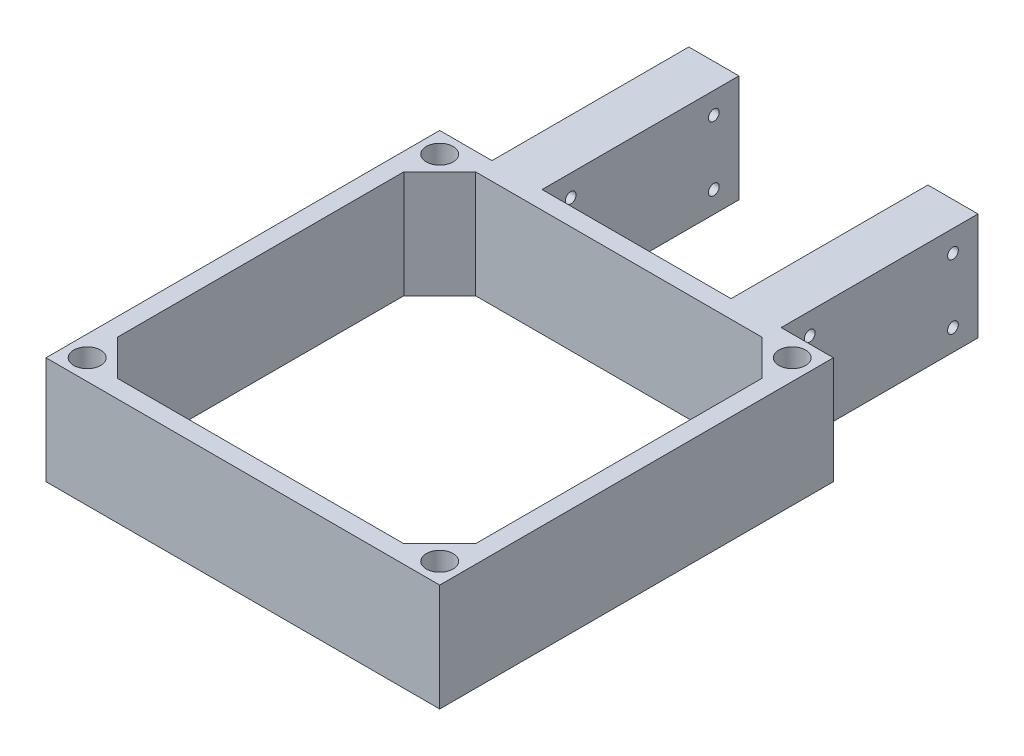
SolidWorks part; units mm, degrees
ref_plane "Front Plane" through (0, 0, 0) normal (0, 0, 1) x (1, 0, 0)
ref_plane "Top Plane" through (0, 0, 0) normal (0, 1, 0) x (1, 0, 0)
ref_plane "Right Plane" through (0, 0, 0) normal (1, 0, 0) x (0, 0, -1)
other "Bounding Box"
ref_plane "Default Plane" through (-8.9266, -12.7485, 0) normal (-0.1736, 0.9848, 0) x (0.9848, 0.1736, 0)
sketch "Sketch1" plane through (0, 0, 0) normal (0, 1, 0) x (1, 0, 0)
  line L0 (-63.5, 50.8) -> (-50.8, 63.5)
  line L1 (69.85, -69.85) -> (-69.85, -69.85)
  line L2 (69.85, -69.85) -> (69.85, 69.85)
  line L3 (69.85, 69.85) -> (-69.85, 69.85)
  line L4 (-69.85, -69.85) -> (-69.85, 69.85)
  line L5 (69.85, -69.85) -> (-69.85, 69.85) construction
  line L6 (69.85, 69.85) -> (-69.85, -69.85) construction
  line L7 (-51.308, 69.85) -> (-33.528, 69.85)
  line L8 (-51.308, 69.85) -> (-51.308, 139.7)
  line L9 (-51.308, 139.7) -> (-33.528, 139.7)
  line L10 (-33.528, 69.85) -> (-33.528, 139.7)
  line L11 (51.308, 69.85) -> (33.528, 69.85)
  line L12 (51.308, 69.85) -> (51.308, 139.7)
  line L13 (51.308, 139.7) -> (33.528, 139.7)
  line L14 (33.528, 69.85) -> (33.528, 139.7)
  line L15 (50.8, -63.5) -> (-50.8, -63.5)
  line L16 (63.5, -50.8) -> (63.5, 50.8)
  line L17 (50.8, 63.5) -> (-50.8, 63.5)
  line L18 (-63.5, -50.8) -> (-63.5, 50.8)
  line L19 (63.5, -63.5) -> (-63.5, 63.5) construction
  line L20 (63.5, 63.5) -> (-63.5, -63.5) construction
  line L21 (63.5, 50.8) -> (50.8, 63.5)
  line L22 (50.8, -63.5) -> (63.5, -50.8)
  line L23 (-50.8, -63.5) -> (-63.5, -50.8)
  circle A0 centre (-62.5475, 62.5475) radius 4.7625
  circle A1 centre (-62.5475, 62.5475) radius 7.3025 construction
  circle A2 centre (62.5475, 62.5475) radius 4.7625
  circle A3 centre (62.5475, 62.5475) radius 7.3025 construction
  circle A4 centre (62.5475, -62.5475) radius 4.7625
  circle A5 centre (62.5475, -62.5475) radius 7.3025 construction
  circle A6 centre (-62.5475, -62.5475) radius 4.7625
  circle A7 centre (-62.5475, -62.5475) radius 7.3025 construction
  point P0 (0, 0)
  point P15 (0, 0)
  dimension "D9" = 9.525
  dimension "D10" = 2.54
  dimension "D1" = 139.7
  dimension "D2" = 139.7
  dimension "D3" = 18.542
  dimension "D4" = 18.542
  dimension "D5" = 17.78
  dimension "D6" = 69.85
  dimension "D7" = 6.35
  dimension "D8" = 6.35
extrude "Boss-Extrude1" add sketch "Sketch1" along normal mid plane 38.1 contours L4 L1 L2 L3 A6 A4 A2 A0 L15 L23 L18 L0 L17 L21 L16 L22 | L3 L10 L9 L8 | L14 L3 L12 L13 region at (0, 0, 67.8743) region at (42.418, 0, -104.775) region at (-42.418, 0, -104.775)
sketch "Sketch2" plane through (51.308, 0, 0) normal (1, 0, 0) x (0, 0, -1)
  line L0 (139.7, 19.05) -> (139.7, -19.05) construction
  line L3 (69.85, 19.05) -> (69.85, -19.05) construction
  line L4 (130.81, -11.43) -> (80.01, -11.43) construction
  line L5 (130.81, -11.43) -> (130.81, 11.43) construction
  line L6 (130.81, 11.43) -> (80.01, 11.43) construction
  line L7 (80.01, -11.43) -> (80.01, 11.43) construction
  line L8 (130.81, -11.43) -> (80.01, 11.43) construction
  line L9 (130.81, 11.43) -> (80.01, -11.43) construction
  line L10 (69.85, -19.05) -> (139.7, -19.05) construction
  circle A0 centre (80.01, 11.43) radius 1.905
  circle A1 centre (130.81, -11.43) radius 1.905
  circle A2 centre (130.81, 11.43) radius 1.905
  circle A3 centre (80.01, -11.43) radius 1.905
  point P6 (105.41, 0)
  dimension "D5" = 3.81
  dimension "D1" = 10.16
  dimension "D2" = 8.89
  dimension "D3" = 22.86
  dimension "D4" = 7.62
extrude "Cut-Extrude1" cut sketch "Sketch2" along direction (-1, 0, 0) on the side against the normal up to surface (102.616 mm away) up to face at (-51.308, 0, -104.775)
